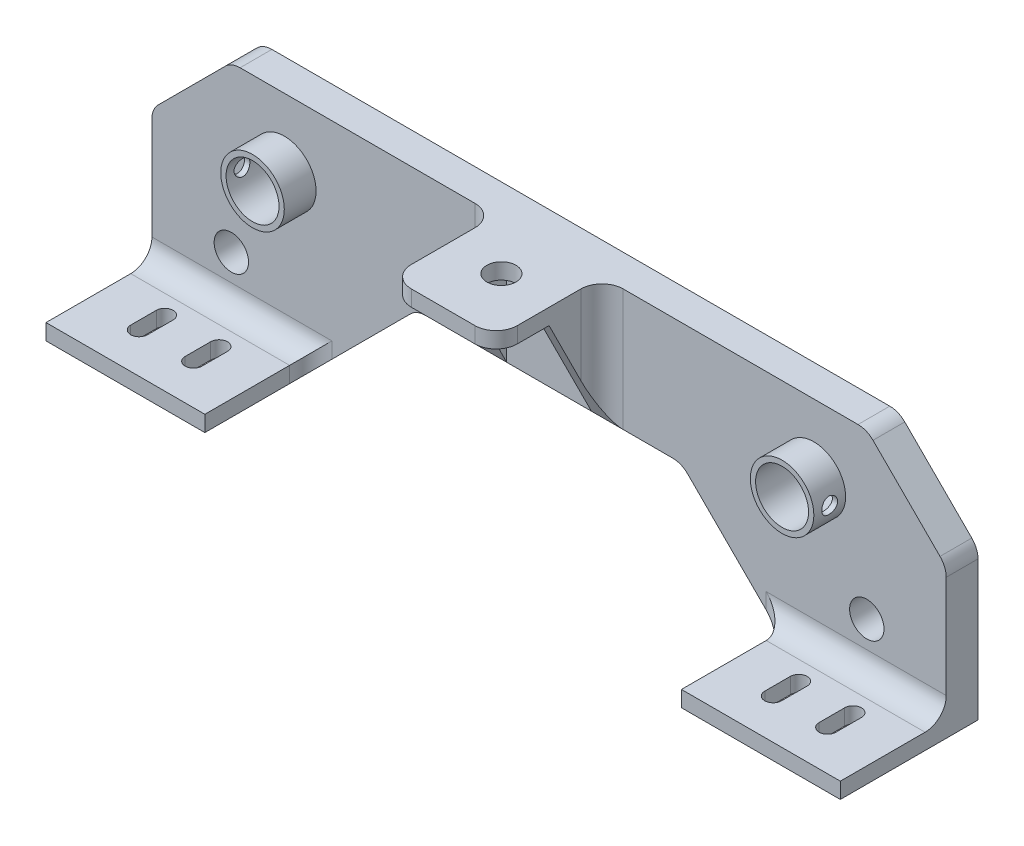
SolidWorks part; units mm, degrees
ref_plane "Alzado" through (0, 0, 0) normal (0, 0, 1) x (1, 0, 0)
ref_plane "Planta" through (0, 0, 0) normal (0, 1, 0) x (1, 0, 0)
ref_plane "Vista lateral" through (0, 0, 0) normal (1, 0, 0) x (0, 0, -1)
sketch "Croquis1" plane through (0, 0, 0) normal (0, 0, 1) x (1, 0, 0)
  line L0 (-50, 30) -> (50, 30) construction
  line L1 (-75, 43) -> (75, 43)
  line L2 (-75, 43) -> (-75, 0)
  line L3 (-75, 0) -> (75, 0)
  line L4 (75, 43) -> (75, 0)
  line L5 (-60, 12) -> (60, 12) construction
  line L6 (-60, 43) -> (-75, 28)
  line L7 (60, 43) -> (75, 28)
  line L8 (-25, 20) -> (-45, 0)
  line L9 (-25, 20) -> (25, 20)
  line L10 (-25, 20) -> (-25, 0)
  line L11 (-25, 0) -> (25, 0)
  line L12 (25, 20) -> (25, 0)
  line L13 (-25, 20) -> (25, 0) construction
  line L14 (-25, 0) -> (25, 20) construction
  line L15 (25, 20) -> (45, 0)
  circle A0 centre (-50, 30) radius 5
  circle A1 centre (50, 30) radius 5
  circle A2 centre (-60, 12) radius 3.25
  circle A3 centre (60, 12) radius 3.25
  point P4 (0, 0)
  point P14 (0, 30)
  point P15 (0, 12)
  point P20 (0, 10)
  point P25 (0, 20)
  dimension "D3" = 10
  dimension "D7" = 6.5
  dimension "D9" = 15
  dimension "D1" = 150
  dimension "D2" = 43
  dimension "D4" = 100
  dimension "D5" = 120
  dimension "D6" = 30
  dimension "D8" = 12
  dimension "D10" = 15
  dimension "D11" = 15
  dimension "D12" = 15
  dimension "D13" = 20
  dimension "D14" = 50
  dimension "D15" = 20
  dimension "D16" = 20
extrude "Saliente-Extruir1" add sketch "Croquis1" along normal blind 6 contours L9 L15 L3 L4 L7 L1 L6 L2 L8 A3 A2 A1 A0 region at (0, 24.3286, 0)
sketch "Croquis2" plane through (0, 0, 6) normal (0, 0, 1) x (1, 0, 0)
  circle A0 centre (-50, 30) radius 6
  circle A1 centre (-50, 30) radius 5
  circle A2 centre (50, 30) radius 6
  circle A3 centre (50, 30) radius 5
  circle A6 centre (-50, 30) radius 5 construction
  circle A7 centre (50, 30) radius 5 construction
  dimension "D1" = 1
extrude "Saliente-Extruir2" add sketch "Croquis2" along normal blind 6
sketch "Croquis4" plane through (0, 0, 6) normal (0, 0, 1) x (1, 0, 0)
  line L1 (-10, 43) -> (10, 43)
  line L2 (-10, 43) -> (-10, 40)
  line L3 (-10, 40) -> (10, 40)
  line L4 (10, 43) -> (10, 40)
  line L5 (-60, 43) -> (60, 43) construction
  point P6 (0, 40)
  dimension "D1" = 20
  dimension "D2" = 3
extrude "Saliente-Extruir3" add sketch "Croquis4" along normal blind 20
sketch "Croquis11" plane through (0, 43, 0) normal (0, 1, 0) x (1, 0, 0)
  circle A0 centre (0, -15) radius 2.75
  dimension "D1" = 5.5
  dimension "D2" = 15
extrude "Cortar-Extruir2" cut sketch "Croquis11" against normal blind 10
sketch "Croquis7" plane through (-10, 0, 0) normal (-1, 0, 0) x (0, 0, 1)
  line L0 (16, 40) -> (6, 20)
  line L1 (26, 40) -> (6, 40) construction
  line L4 (6, 43) -> (0, 43) construction
  line L5 (6, 28) -> (6, 0) construction
  dimension "D1" = 23
rib "Nervio2" sketch "Croquis7" sketch "Croquis7" thickness 2 extrusion direction parallel to sketch draft on no parameters "D1"=2
sketch "Croquis8" plane through (0, 0, 6) normal (0, 0, 1) x (1, 0, 0)
  line L0 (-75, 0) -> (-45, 0) construction
  line L1 (-75, 0) -> (-45, 0)
  line L2 (-75, 0) -> (-75, 3)
  line L3 (-75, 3) -> (-45, 3)
  line L4 (-45, 0) -> (-45, 3)
  dimension "D1" = 3
extrude "Saliente-Extruir4" add sketch "Croquis8" along normal blind 20
hole_wizard "Diámetro de taladro 1/8 (0.125)2" positions "Croquis9" profile "Croquis10" size "1/8" standard "Ansi Inch" slot yes end condition up to next
sketch "Croquis9" plane through (0, 3, 0) normal (0, 1, 0) x (1, 0, 0)
  line L0 (-65, -20) -> (-65, -12) construction
  line L1 (-75, -26) -> (-75, -6) construction
  point P0 (-65, -16)
  point P8 (-54.7297, -16)
  point P16 (-75, -16)
  dimension "D1" = 8
  dimension "D2" = 10.2703
  dimension "D3" = 10
sketch "Croquis10" plane through (-65, 3, 16) normal (1, 0, 0) x (0, 0, 1)
  line L0 (0, 0) -> (0, 3.001)
  line L1 (0, 3.001) -> (1.5875, 3.001)
  line L2 (1.5875, 3.001) -> (1.5875, 0)
  line L5 (1.5875, 0) -> (0, 0)
  line L11 (0, -6.35) -> (0, 107.95) construction
  dimension "Diámetro de taladro hasta el siguiente" = 3.175
  dimension "Profundidad de taladro hasta el siguiente" = 3.001
ref_plane "Plano1" through (-50, 0, 0) normal (1, 0, 0) x (0, 0, -1)
sketch "Croquis12" plane through (-50, 0, 0) normal (1, 0, 0) x (0, 0, -1)
  line L0 (-12, 30) -> (0, 30) construction
  line L1 (-6, 43) -> (-6, 28) construction
  circle A0 centre (-9, 30) radius 1.5
  dimension "D1" = 3
  dimension "D2" = 3
extrude "Cortar-Extruir3" cut sketch "Croquis12" against normal blind 10
mirror "Simetría2" about plane through (0, 0, 0) normal (1, 0, 0) of "Cortar-Extruir3", "Nervio2", "Saliente-Extruir4", "Diámetro de taladro 1/8 (0.125)2"
fillet "Redondeo1" radius 4 14 edges at (-75, 28, 3) (-60, 43, 3) (-10, 31.5, 6) (75, 28, 3) (60, 43, 3) (10, 31.5, 6) (-45, 1.5, 6) (45, 1.5, 6) (60, 3, 6) (-60, 3, 6) (25, 20, 3) (-25, 20, 3) (10, 41.5, 26) (-10, 41.5, 26)
